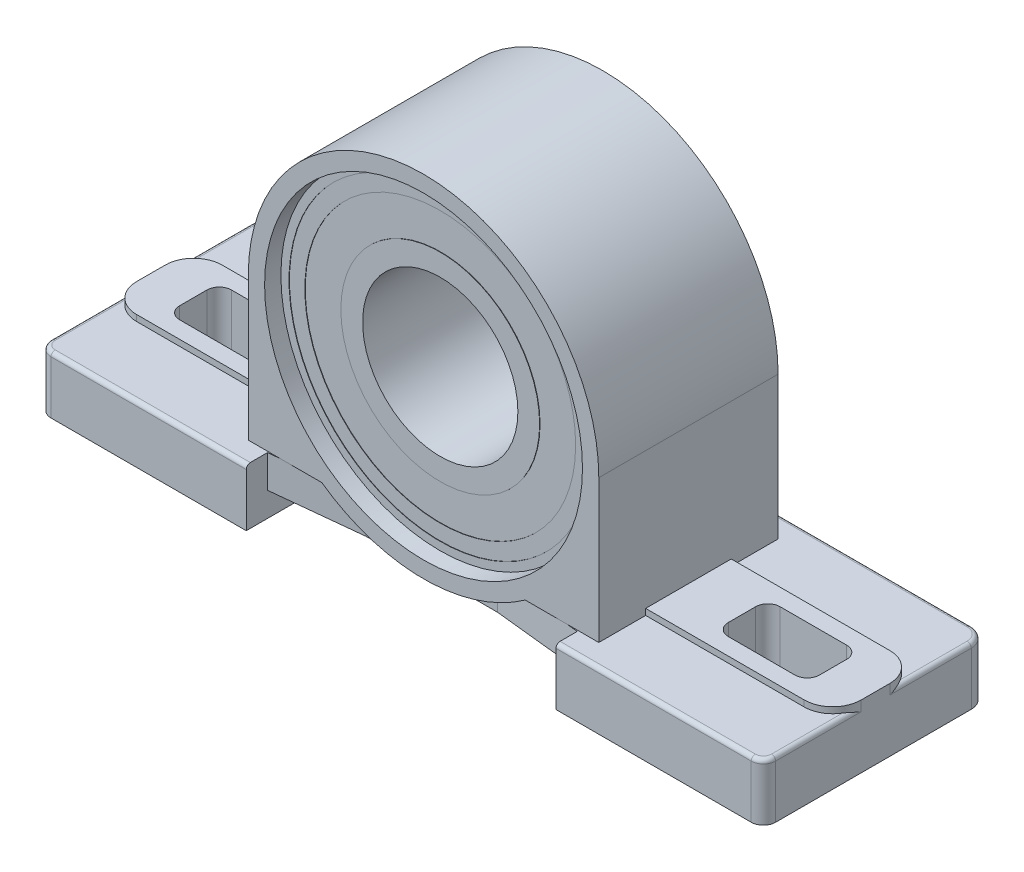
SolidWorks part; units mm, degrees
ref_plane "Alzado" through (0, 0, 0) normal (0, 0, 1) x (1, 0, 0)
ref_plane "Planta" through (0, 0, 0) normal (0, 1, 0) x (1, 0, 0)
ref_plane "Vista lateral" through (0, 0, 0) normal (1, 0, 0) x (0, 0, -1)
sketch "Croquis1" plane through (0, 0, 0) normal (0, 1, 0) x (1, 0, 0)
  line L1 (0, 0) -> (177.8, 0)
  line L2 (0, 0) -> (0, -55)
  line L3 (0, -55) -> (177.8, -55)
  line L4 (177.8, 0) -> (177.8, -55)
  dimension "D1" = 177.8
  dimension "D2" = 55
extrude "Saliente-Extruir1" add sketch "Croquis1" along normal blind 14
sketch "Croquis2" plane through (0, 0, 55) normal (0, 0, 1) x (1, 0, 0)
  line L0 (88.9, 0) -> (88.9, 49.022) construction
  line L1 (0, 0) -> (177.8, 0) construction
  line L2 (45.9, 49.022) -> (45.9, 13)
  line L3 (131.9, 49.022) -> (131.9, 13)
  line L4 (45.9, 13) -> (131.9, 13)
  circle A0 centre (88.9, 49.022) radius 19.05
  arc A1 (131.9, 49.022) -> (45.9, 49.022) centre (88.9, 49.022) ccw
  dimension "D2" = 38.1
  dimension "D3" = 86
  dimension "D1" = 49.022
extrude "Saliente-Extruir2" add sketch "Croquis2" against normal up to surface (55 mm away) up to face at (88.9, 7, 0)
sketch "Croquis3" plane through (0, 14, 0) normal (0, 1, 0) x (1, 0, 0)
  line L0 (177.8, 0) -> (131.9, 0) construction
  line L1 (136.0613, 0) -> (33.6198, 0)
  line L2 (136.0613, 0) -> (136.0613, -5.5)
  line L3 (136.0613, -5.5) -> (33.6198, -5.5)
  line L4 (33.6198, 0) -> (33.6198, -5.5)
  line L5 (131.9, -55) -> (177.8, -55) construction
  line L6 (136.0613, -55) -> (33.6198, -55)
  line L7 (136.0613, -55) -> (136.0613, -49.5)
  line L8 (136.0613, -49.5) -> (33.6198, -49.5)
  line L9 (33.6198, -55) -> (33.6198, -49.5)
  dimension "D1" = 5.5
  dimension "D2" = 5.5
extrude "Cortar-Extruir1" cut sketch "Croquis3" along normal blind 88
sketch "Croquis4" plane through (0, 0, 0) normal (0, -1, 0) x (1, 0, 0)
  line L0 (177.8, 0) -> (0, 0) construction
  line L1 (126.9, 0) -> (50.9, 0)
  line L2 (126.9, 0) -> (126.9, 55)
  line L3 (126.9, 55) -> (50.9, 55)
  line L4 (50.9, 0) -> (50.9, 55)
  line L5 (0, 55) -> (177.8, 55) construction
  line L6 (131.9, 49.5) -> (131.9, 5.5) construction
  line L7 (45.9, 5.5) -> (45.9, 49.5) construction
  dimension "D1" = 5
  dimension "D2" = 5
extrude "Cortar-Extruir2" cut sketch "Croquis4" against normal blind 6
sketch "Croquis5" plane through (0, 6, 0) normal (0, -1, 0) x (1, 0, 0)
  line L0 (126.9, 0) -> (126.9, 55) construction
  line L1 (50.9, 0) -> (126.9, 0)
  line L2 (50.9, 0) -> (50.9, 5.5)
  line L3 (50.9, 5.5) -> (126.9, 5.5)
  line L4 (126.9, 0) -> (126.9, 5.5)
  line L5 (45.9, 5.5) -> (131.9, 5.5) construction
  line L6 (131.9, 49.5) -> (45.9, 49.5) construction
  line L7 (50.9, 55) -> (126.9, 55)
  line L8 (50.9, 55) -> (50.9, 49.5)
  line L9 (50.9, 49.5) -> (126.9, 49.5)
  line L10 (126.9, 55) -> (126.9, 49.5)
extrude "Cortar-Extruir3" cut sketch "Croquis5" against normal blind 20
sketch "Croquis6" plane through (0, 0, 49.5) normal (0, 0, 1) x (1, 0, 0)
  circle A0 centre (88.9, 49.022) radius 39
  dimension "D1" = 78
extrude "Cortar-Extruir4" cut sketch "Croquis6" against normal blind 4
sketch "Croquis7" plane through (0, 0, 5.5) normal (0, 0, -1) x (-1, 0, 0)
  circle A0 centre (-88.9, 49.022) radius 39
extrude "Cortar-Extruir5" cut sketch "Croquis7" against normal blind 4
sketch "Croquis8" plane through (0, 0, 9.5) normal (0, 0, -1) x (-1, 0, 0)
  circle A0 centre (-88.9, 49.022) radius 37
  dimension "D1" = 74
extrude "Cortar-Extruir6" cut sketch "Croquis8" against normal blind 0.1
sketch "Croquis9" plane through (0, 0, 9.6) normal (0, 0, -1) x (-1, 0, 0)
  circle A0 centre (-88.9, 49.022) radius 24.3933
  circle A1 centre (-88.9, 49.022) radius 19.05
extrude "Saliente-Extruir3" add sketch "Croquis9" along normal blind 12
sketch "Croquis11" plane through (0, 0, 9.6) normal (0, 0, -1) x (-1, 0, 0)
  circle A0 centre (-88.9, 49.022) radius 24.3933
  circle A1 centre (-88.9, 49.022) radius 33.2237
extrude "Cortar-Extruir7" cut sketch "Croquis11" against normal blind 0.1
fillet "Redondeo1" radius 3 3 edges at (177.8, 7, 55) (0, 7, 55) (0, 7, 0)
sketch "Croquis12" plane through (0, 0, 45.5) normal (0, 0, 1) x (1, 0, 0)
  circle A0 centre (88.9, 49.022) radius 37
extrude "Cortar-Extruir8" cut sketch "Croquis12" against normal blind 0.1
sketch "Croquis13" plane through (0, 0, 45.4) normal (0, 0, 1) x (1, 0, 0)
  circle A0 centre (88.9, 49.022) radius 24.3933
  circle A1 centre (88.9, 49.022) radius 33.2237
extrude "Cortar-Extruir9" cut sketch "Croquis13" against normal blind 0.1
sketch "Croquis15" plane through (0, 0, 49.5) normal (0, 0, 1) x (1, 0, 0)
  line L0 (50.9, 14) -> (63.9509, 14)
  line L1 (126.9, 14) -> (126.9, 6)
  line L2 (126.9, 6) -> (50.9, 6)
  line L3 (50.9, 6) -> (50.9, 14)
  line L4 (113.8491, 14) -> (126.9, 14)
  arc A0 (63.9509, 14) -> (113.8491, 14) centre (88.9, 49.022) ccw
extrude "Cortar-Extruir10" cut sketch "Croquis15" against normal blind 2
chamfer "Chaflán1" distance 2.3 angle 84 2 edges at (126.9, 10, 47.5) (50.9, 10, 47.5) first distance on face at (126.9, 9.1111, 29.5) first distance on face at (50.9, 9.1111, 29.5)
sketch "Croquis16" plane through (0, 0, 5.5) normal (0, 0, -1) x (-1, 0, 0)
  line L0 (-126.9, 14) -> (-113.8491, 14)
  line L1 (-50.9, 14) -> (-50.9, 6)
  line L2 (-50.9, 6) -> (-126.9, 6)
  line L3 (-126.9, 6) -> (-126.9, 14)
  line L4 (-63.9509, 14) -> (-50.9, 14)
  arc A0 (-113.8491, 14) -> (-63.9509, 14) centre (-88.9, 49.022) ccw
extrude "Cortar-Extruir11" cut sketch "Croquis16" against normal blind 2
chamfer "Chaflán2" distance 2.3 angle 84 2 edges at (50.9, 10, 7.5) (126.9, 10, 7.5) first distance on face at (50.9, 9.1111, 25.5667) first distance on face at (126.9, 9.1111, 25.5667)
fillet "Redondeo3" radius 4 1 edges at (177.8, 7, 0)
sketch "Croquis17" plane through (0, 14, 0) normal (0, 1, 0) x (1, 0, 0)
  line L0 (88.9, -49.5) -> (88.9, -5.5) construction
  line L1 (45.9, -49.5) -> (131.9, -49.5) construction
  line L2 (131.9, -5.5) -> (45.9, -5.5) construction
  line L3 (126.9, -55) -> (174.8, -55) construction
  line L4 (10.414, -33.85) -> (32.766, -21.15) construction
  line L5 (167.386, -21.15) -> (145.034, -21.15)
  line L6 (167.386, -21.15) -> (167.386, -33.85)
  line L7 (167.386, -33.85) -> (145.034, -33.85)
  line L8 (145.034, -21.15) -> (145.034, -33.85)
  line L9 (167.386, -21.15) -> (145.034, -33.85) construction
  line L10 (167.386, -33.85) -> (145.034, -21.15) construction
  line L11 (10.414, -21.15) -> (32.766, -33.85) construction
  line L12 (32.766, -21.15) -> (32.766, -33.85)
  line L13 (10.414, -33.85) -> (32.766, -33.85)
  line L14 (10.414, -21.15) -> (10.414, -33.85)
  line L15 (10.414, -21.15) -> (32.766, -21.15)
  point P6 (156.21, -27.5)
  dimension "D1" = 27.5
  dimension "D2" = 22.352
  dimension "D3" = 12.7
extrude "Cortar-Extruir12" cut sketch "Croquis17" against normal up to surface (14 mm away) up to face at (17.7596, 0, 27.5)
fillet "Redondeo4" radius 3 8 edges at (10.414, 7, 21.15) (10.414, 7, 33.85) (32.766, 7, 33.85) (32.766, 7, 21.15) (167.386, 7, 21.15) (145.034, 7, 21.15) (145.034, 7, 33.85) (167.386, 7, 33.85)
sketch "Croquis18" plane through (0, 14, 0) normal (0, 1, 0) x (1, 0, 0)
  line L0 (0, -27.5) -> (88.9, -27.5) construction
  line L5 (0, -3) -> (0, -52) construction
  line L6 (45.9, -38) -> (7, -38)
  line L7 (45.9, -5.5) -> (45.9, -49.5) construction
  line L8 (0, -31) -> (0, -27.5)
  line L9 (0, -27.5) -> (0, -24)
  line L10 (7, -17) -> (45.9, -17)
  line L11 (45.9, -17) -> (45.9, -27.5)
  line L12 (45.9, -27.5) -> (45.9, -38)
  line L13 (88.9, -49.5) -> (88.9, -27.5) construction
  line L14 (45.9, -49.5) -> (131.9, -49.5) construction
  line L15 (29.766, -33.85) -> (13.414, -33.85)
  line L16 (32.766, -30.85) -> (32.766, -24.15)
  line L17 (29.766, -21.15) -> (13.414, -21.15)
  line L18 (10.414, -24.15) -> (10.414, -30.85)
  line L19 (167.386, -24.15) -> (167.386, -30.85)
  line L20 (148.034, -21.15) -> (164.386, -21.15)
  line L21 (145.034, -30.85) -> (145.034, -24.15)
  line L22 (148.034, -33.85) -> (164.386, -33.85)
  line L23 (131.9, -27.5) -> (131.9, -38)
  line L24 (131.9, -17) -> (131.9, -27.5)
  line L25 (170.8, -17) -> (131.9, -17)
  line L26 (177.8, -27.5) -> (177.8, -24)
  line L27 (177.8, -31) -> (177.8, -27.5)
  line L28 (131.9, -38) -> (170.8, -38)
  arc A0 (0, -24) -> (7, -17) centre (7, -24) cw
  arc A1 (7, -38) -> (0, -31) centre (7, -31) cw
  arc A2 (29.766, -33.85) -> (32.766, -30.85) centre (29.766, -30.85) ccw
  arc A3 (32.766, -24.15) -> (29.766, -21.15) centre (29.766, -24.15) ccw
  arc A4 (13.414, -21.15) -> (10.414, -24.15) centre (13.414, -24.15) ccw
  arc A5 (10.414, -30.85) -> (13.414, -33.85) centre (13.414, -30.85) ccw
  arc A6 (164.386, -21.15) -> (167.386, -24.15) centre (164.386, -24.15) cw
  arc A7 (145.034, -24.15) -> (148.034, -21.15) centre (148.034, -24.15) cw
  arc A8 (148.034, -33.85) -> (145.034, -30.85) centre (148.034, -30.85) cw
  arc A9 (170.8, -38) -> (177.8, -31) centre (170.8, -31) ccw
  arc A10 (177.8, -24) -> (170.8, -17) centre (170.8, -24) ccw
  arc A11 (167.386, -30.85) -> (164.386, -33.85) centre (164.386, -30.85) cw
  point P16 (0, -17)
  point P19 (0, -38)
  point P61 (177.8, -38)
  point P62 (177.8, -17)
  dimension "D3" = 7
  dimension "D1" = 10.5
  dimension "D2" = 10.5
extrude "Saliente-Extruir4" add sketch "Croquis18" along normal blind 1.5
fillet "Redondeo5" radius 1 10 edges at (177.8, 14, 41.5) (176.9213, 14, 54.1213) (177.8, 14, 14) (176.6284, 14, 1.1716) (0, 14, 41.5) (0.8787, 14, 54.1213) (0, 14, 13.5) (0.8787, 14, 0.8787) (150.85, 14, 55) (150.35, 14, 0)
